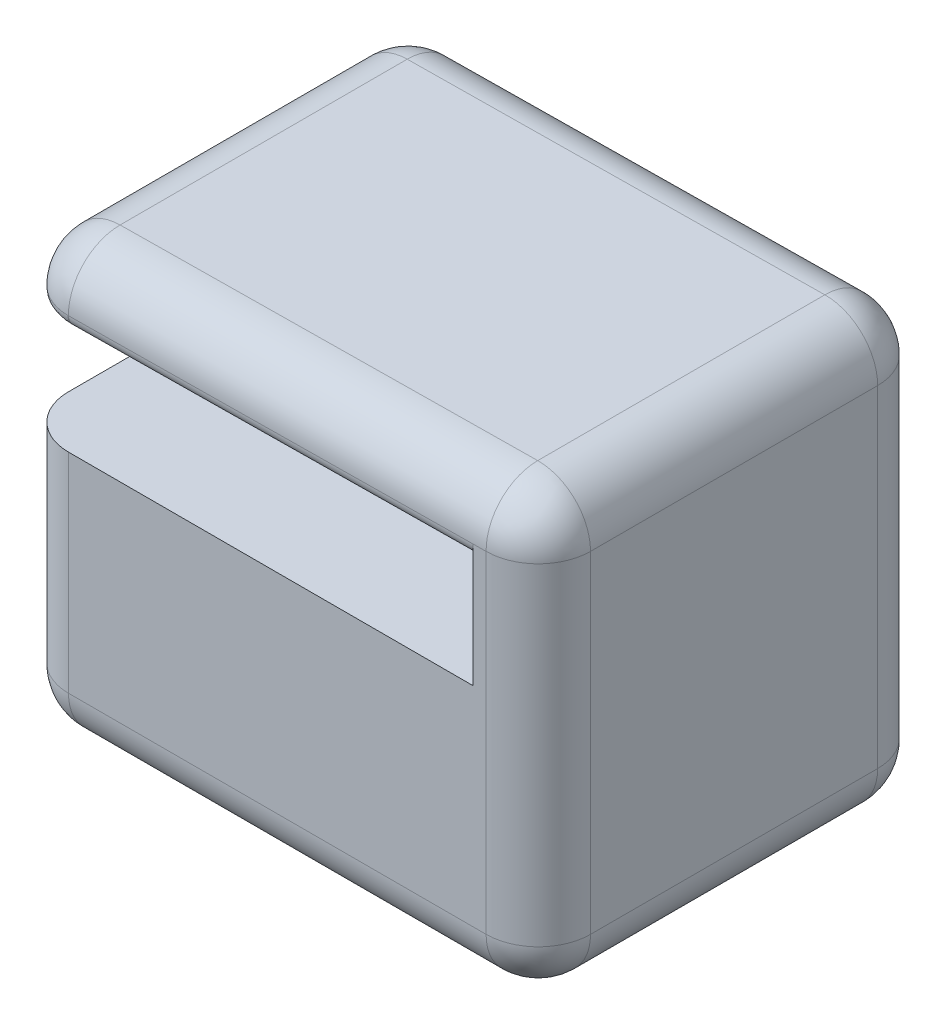
SolidWorks part; units mm, degrees
ref_plane "Front Plane" through (0, 0, 0) normal (0, 0, 1) x (1, 0, 0)
ref_plane "Top Plane" through (0, 0, 0) normal (0, 1, 0) x (1, 0, 0)
ref_plane "Right Plane" through (0, 0, 0) normal (1, 0, 0) x (0, 0, -1)
sketch "Sketch1" plane through (0, 0, 0) normal (0, 0, 1) x (1, 0, 0)
  line L1 (0, -10.6226) -> (-25.3983, -10.6226)
  line L2 (0, -10.6226) -> (0, 10.6226)
  line L3 (0, 10.6226) -> (-25.3983, 10.3324)
  line L4 (-25.3983, -10.6226) -> (-25.3983, 10.3324)
  line L5 (-25.3983, 7.1574) -> (-3.175, 7.1574) construction
  line L6 (-25.3983, 7.1574) -> (-25.3983, 2.0774) construction
  line L7 (-25.3983, 2.0774) -> (-3.175, 2.0774) construction
  line L8 (-3.175, 7.1574) -> (-3.175, 2.0774) construction
  line L12 (-25.3983, 7.1574) -> (-25.3983, 2.0774)
  line L13 (-25.3983, 2.0774) -> (-3.175, 2.0774)
  line L14 (-3.175, 2.0774) -> (-3.175, 7.4114)
  line L15 (-3.175, 7.4114) -> (-25.3983, 7.1574)
  point P6 (0, 0)
  dimension "D1" = 5.08
  dimension "D3" = 12.7
  dimension "D4" = 25.4
  dimension "D5" = 3.175
  dimension "D6" = 5.334
  dimension "D2" = 3.175
extrude "Boss-Extrude1" add sketch "Sketch1" along normal blind 19.05 contours L5 L8 L7 L4 L1 L2 L3 region at (-12.2497, -1.3816, 0)
sketch "Sketch4" plane through (0, -10.6226, 0) normal (0, 1, 0) x (1, 0, 0)
  line L0 (-12.7, 0) -> (-12.7, -19.05) construction
  line L1 (-25.3983, -19.05) -> (-25.3983, 0) construction
  circle A0 centre (-12.7, -19.05) radius 1.5
  circle A1 centre (-12.7, 0) radius 1.5
  point P4 (-12.7, -9.525)
  point P7 (-25.3983, -9.525)
  dimension "D1" = 3
  dimension "D2" = 19.05
  dimension "D3" = 9.525
extrude "Cut-Extrude2" [suppressed] cut sketch "Sketch4" along normal up to surface (12.7 mm away)
sketch "Sketch6" plane through (-0.1214, 10.6213, 0) normal (-0.0114, 0.9999, 0) x (0.9999, 0.0114, 0)
  line L0 (-12.6761, -19.05) -> (-12.6761, 0) construction
  line L6 (-3.1511, -19.05) -> (-3.1511, 0) construction
  line L7 (-25.2786, -19.05) -> (-25.2786, 0) construction
  circle A0 centre (-12.6761, -19.05) radius 1.5
  circle A1 centre (-12.6761, 0) radius 1.5
  point P6 (-12.6761, -9.525)
  point P9 (-25.2786, -9.525)
  dimension "D3" = 3
  dimension "D1" = 19.05
  dimension "D2" = 9.525
extrude "Cut-Extrude4" [suppressed] cut sketch "Sketch6" against normal up to surface (3.1745 mm away)
fillet "Fillet1" radius 2.54 14 edges at (-25.3983, -10.6226, 9.525) (-12.6992, -10.6226, 0) (-12.6992, 10.4775, 0) (-25.3983, 10.3324, 9.525) (-12.6992, 10.4775, 19.05) (-12.6992, -10.6226, 19.05) (0, -10.6226, 9.525) (0, 10.6226, 9.525) (0, 0, 0) (0, 0, 19.05) (-25.3983, -4.2726, 19.05) (-25.3983, -4.2726, 0) (-25.3983, 8.7449, 0) (-25.3983, 8.7449, 19.05)
sketch "Sketch2" plane through (-0.1214, 10.6213, 0) normal (-0.0114, 0.9999, 0) x (0.9999, 0.0114, 0)
  line L0 (-22.7675, -2.54) -> (-22.7675, -16.51) construction
  line L1 (-19.0826, 0.8) -> (-6.1326, 0.8)
  line L2 (-19.3326, 0.55) -> (-19.3326, -19.6)
  line L3 (-19.0826, -19.85) -> (-6.1326, -19.85)
  line L4 (-5.8826, 0.55) -> (-5.8826, -19.6)
  line L5 (-2.4478, -2.54) -> (-22.7675, -2.54) construction
  arc A0 (-6.1326, -19.85) -> (-5.8826, -19.6) centre (-6.1326, -19.6) ccw
  arc A1 (-19.3326, -19.6) -> (-19.0826, -19.85) centre (-19.0826, -19.6) ccw
  arc A2 (-6.1326, 0.8) -> (-5.8826, 0.55) centre (-6.1326, 0.55) cw
  arc A3 (-19.0826, 0.8) -> (-19.3326, 0.55) centre (-19.0826, 0.55) ccw
  point P4 (-19.3326, -9.525)
  point P7 (-22.7675, -9.525)
  point P9 (-12.6076, 0.8)
  point P12 (-12.6076, -2.54)
  point P14 (-5.8826, -19.85)
  point P16 (-5.8826, -19.85)
  point P20 (-5.8826, 0.8)
  point P23 (-19.3326, 0.8)
  dimension "D3" = 0.25
  dimension "D4" = 0.25
  dimension "D5" = 0.25
  dimension "D1" = 13.45
  dimension "D2" = 20.65
extrude "Cut-Extrude1" [suppressed] cut sketch "Sketch2" against normal blind 4.7625
fillet "Fillet2" radius 0.635 5 edges at (-13.0167, 7.2989, 19.05) (-24.6544, 7.1659, 18.3061) (-13.0167, 7.2989, 0) (-24.6544, 7.1659, 0.7439) (-25.3983, 7.1574, 9.525)
equation "\"bottomThickness\"= .220in"
equation "\"wallThickness\"= .118in"
equation "\"D6@Sketch1\"=\"bottomThickness\"-.01in"
equation "\"D1@Sketch1\"=\"bottomThickness\"-.02in"
